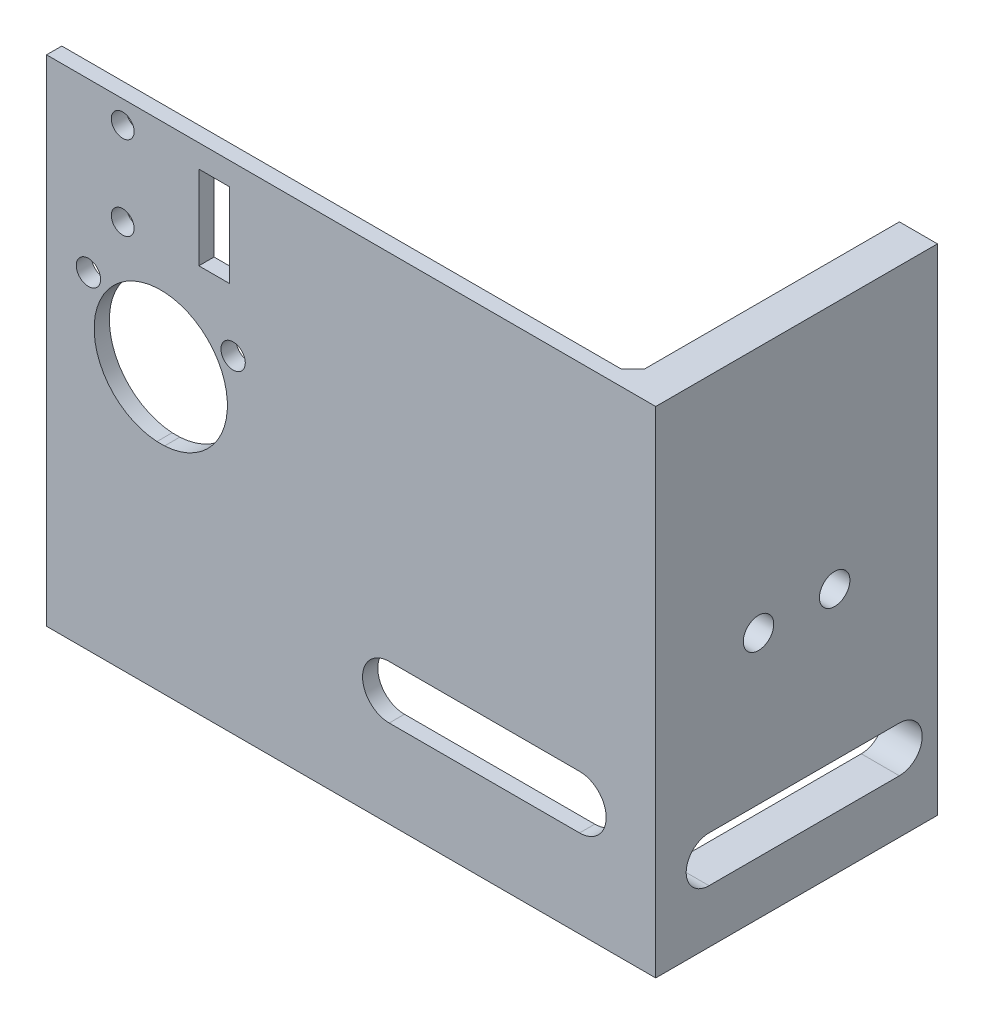
SolidWorks part; units mm, degrees
ref_plane "前视基准面" through (0, 0, 0) normal (0, 0, 1) x (1, 0, 0)
ref_plane "上视基准面" through (0, 0, 0) normal (0, 1, 0) x (1, 0, 0)
ref_plane "右视基准面" through (0, 0, 0) normal (1, 0, 0) x (0, 0, -1)
other "Configuration Table"
sketch "草图1" plane through (0, 0, 0) normal (0, 0, 1) x (1, 0, 0)
  line L1 (-15, 24) -> (15, 24)
  line L2 (-15, 24) -> (-15, -24)
  line L3 (-15, -24) -> (15, -24)
  line L4 (15, 24) -> (15, -24)
  line L5 (-15, 24) -> (15, -24) construction
  line L6 (-15, -24) -> (15, 24) construction
  point P0 (0, 0)
  dimension "D1" = 30
  dimension "D2" = 48
extrude "凸台-拉伸1" add sketch "草图1" against normal blind 2
sketch "草图2" plane through (0, 0, 0) normal (0, 0, 1) x (1, 0, 0)
  line L0 (-9.5, 24) -> (-9.5, -24) construction
  line L1 (15, 24) -> (-15, 24) construction
  line L2 (-15, -24) -> (15, -24) construction
  line L3 (9.5, 24) -> (9.5, -24) construction
  line L4 (15, -24) -> (15, 24) construction
  line L5 (-15, 19) -> (15, 19) construction
  line L6 (-15, 24) -> (-15, -24) construction
  circle A0 centre (-9.5, 19) radius 1.6
  circle A1 centre (9.5, 19) radius 1.6
  point P16 (-9.5, 19)
  point P17 (9.5, 19)
  dimension "D5" = 3.2
  dimension "D1" = 19
  dimension "D2" = 5.5
  dimension "D3" = 5
extrude "切除-拉伸1" cut sketch "草图2" against normal blind 2
sketch "草图3" plane through (0, 0, 0) normal (0, 0, 1) x (1, 0, 0)
  line L0 (-15, 13) -> (15, 13) construction
  line L1 (-15, 24) -> (-15, -24) construction
  line L2 (15, -24) -> (15, 24) construction
  line L4 (-11.1, 19) -> (15, 19) construction
  circle A0 centre (-9.5, 19) radius 1.6 construction
  circle A1 centre (0, 13) radius 8.75
  dimension "D2" = 17.5
  dimension "D1" = 6
extrude "切除-拉伸2" cut sketch "草图3" against normal blind 2
sketch "草图4" plane through (0, 24, 0) normal (0, 1, 0) x (1, 0, 0)
  line L4 (-15, 0) -> (15, 0)
  line L5 (15, 0) -> (15, 2)
  line L6 (15, 2) -> (-15, 2)
  line L7 (-15, 2) -> (-15, 0)
  line L8 (-15, 0) -> (15, 0)
  line L9 (15, 0) -> (15, 2)
  line L10 (15, 2) -> (-15, 2)
  line L11 (-15, 2) -> (-15, 0)
  dimension "D1" = 0
extrude "凸台-拉伸2" add sketch "草图4" along normal blind 17
sketch "草图14" plane through (0, -24, 0) normal (0, -1, 0) x (1, 0, 0)
  line L0 (0, 0) -> (0, -2) construction
  line L1 (-15, 0) -> (15, 0) construction
  line L2 (-15, -2) -> (15, -2) construction
  line L4 (0, 0) -> (-0.5, 0)
  line L5 (0, 0) -> (0, -2)
  line L6 (0, -2) -> (-0.5, -2)
  line L7 (-0.5, 0) -> (-0.5, -2)
  dimension "D1" = 0.5
extrude "切除-拉伸6" cut sketch "草图14" against normal through all
sketch "草图15" plane through (15, 0, 0) normal (1, 0, 0) x (0, 0, -1)
  line L4 (0, 41) -> (0, -24)
  line L5 (0, -24) -> (2, -24)
  line L6 (2, -24) -> (2, 41)
  line L7 (2, 41) -> (0, 41)
  line L8 (0, 41) -> (0, -24)
  line L9 (0, -24) -> (2, -24)
  line L10 (2, -24) -> (2, 41)
  line L11 (2, 41) -> (0, 41)
  dimension "D1" = 0
extrude "凸台-拉伸7" add sketch "草图15" along normal blind 50
sketch "草图16" plane through (0, 0, -2) normal (0, 0, -1) x (-1, 0, 0)
  line L0 (-60, 41) -> (-60, -24) construction
  line L1 (-65, 41) -> (0, 41) construction
  line L2 (0, -24) -> (-65, -24) construction
  line L3 (-65, -24) -> (-65, 41) construction
  line L5 (-65, 41) -> (-60, 41)
  line L6 (-65, 41) -> (-65, -24)
  line L7 (-65, -24) -> (-60, -24)
  line L8 (-60, 41) -> (-60, -24)
  dimension "D1" = 5
extrude "凸台-拉伸8" add sketch "草图16" along normal blind 35
sketch "草图17" plane through (65, 0, 0) normal (1, 0, 0) x (0, 0, -1)
  line L0 (37, 8.5) -> (0, 8.5) construction
  line L1 (37, 41) -> (37, -24) construction
  line L2 (0, 41) -> (0, -24) construction
  line L3 (18.5, 41) -> (18.5, -24) construction
  line L4 (37, 41) -> (0, 41) construction
  line L5 (0, -24) -> (37, -24) construction
  line L6 (13.5, 41) -> (13.5, -24) construction
  line L7 (23.5, 41) -> (23.5, -24) construction
  circle A0 centre (13.5, 8.5) radius 2
  circle A1 centre (23.5, 8.5) radius 2
  point P16 (13.5, 8.5)
  point P17 (23.5, 8.5)
  dimension "D3" = 4
  dimension "D1" = 10
  dimension "D2" = 5
extrude "切除-拉伸7" cut sketch "草图17" against normal blind 35
sketch "草图18" plane through (-0.5, 0, 0) normal (1, 0, 0) x (0, 0, -1)
  line L4 (0, 4.2643) -> (0, -24)
  line L5 (0, -24) -> (2, -24)
  line L6 (2, -24) -> (2, 4.2643)
  line L7 (2, 4.2643) -> (0, 4.2643)
  line L8 (0, 4.2643) -> (0, -24)
  line L9 (0, -24) -> (2, -24)
  line L10 (2, -24) -> (2, 4.2643)
  line L11 (2, 4.2643) -> (0, 4.2643)
  dimension "D1" = 0
extrude "凸台-拉伸9" add sketch "草图18" along normal up to next
sketch "草图19" plane through (-0.5, 0, 0) normal (1, 0, 0) x (0, 0, -1)
  line L4 (2, 21.7357) -> (2, 41)
  line L5 (2, 41) -> (0, 41)
  line L6 (0, 41) -> (0, 21.7357)
  line L7 (0, 21.7357) -> (2, 21.7357)
  line L8 (2, 21.7357) -> (2, 41)
  line L9 (2, 41) -> (0, 41)
  line L10 (0, 41) -> (0, 21.7357)
  line L11 (0, 21.7357) -> (2, 21.7357)
  dimension "D1" = 0
extrude "凸台-拉伸10" add sketch "草图19" along normal up to next
sketch "草图20" plane through (0, 0, 0) normal (0, 0, 1) x (1, 0, 0)
  line L0 (30, 41) -> (30, -24) construction
  line L1 (-15, 41) -> (65, 41) construction
  line L2 (-15, -24) -> (65, -24) construction
  line L3 (-15, -9) -> (65, -9) construction
  line L4 (-15, 41) -> (-15, -24) construction
  line L5 (65, 41) -> (65, -24) construction
  line L6 (55, 41) -> (55, -24) construction
  line L7 (30, -9) -> (55, -9) construction
  line L8 (30, -5.5) -> (55, -5.5)
  line L9 (30, -12.5) -> (55, -12.5)
  arc A0 (30, -5.5) -> (30, -12.5) centre (30, -9) ccw
  arc A1 (55, -12.5) -> (55, -5.5) centre (55, -9) ccw
  point P14 (30, -9)
  point P15 (55, -9)
  point P18 (42.5, -9)
  dimension "D4" = 3.5
  dimension "D1" = 25
  dimension "D2" = 10
  dimension "D3" = 15
extrude "切除-拉伸8" cut sketch "草图20" against normal blind 6
sketch "草图21" plane through (65, 0, 0) normal (1, 0, 0) x (0, 0, -1)
  line L0 (0, -14) -> (37, -14) construction
  line L1 (0, 41) -> (0, -24) construction
  line L2 (37, 41) -> (37, -24) construction
  line L3 (7, 40.7245) -> (7, -24) construction
  line L4 (0, -24) -> (37, -24) construction
  line L5 (32, 41) -> (32, -24) construction
  line L6 (37, 41) -> (0, 41) construction
  line L7 (7, -14) -> (32, -14) construction
  line L8 (7, -11) -> (32, -11)
  line L9 (7, -17) -> (32, -17)
  arc A0 (7, -11) -> (7, -17) centre (7, -14) ccw
  arc A1 (32, -17) -> (32, -11) centre (32, -14) ccw
  point P14 (7, -14)
  point P15 (32, -14)
  point P18 (19.5, -14)
  dimension "D4" = 3
  dimension "D1" = 25
  dimension "D2" = 5
  dimension "D3" = 10
extrude "切除-拉伸9" cut sketch "草图21" against normal blind 6
chamfer "倒角1" distance 1.5 angle 45 1 edges at (60, 8.5, -2)
sketch "草图22" plane through (0, 0, 0) normal (0, 0, 1) x (1, 0, 0)
  line L0 (-15, 38) -> (65, 38) construction
  line L1 (-15, 41) -> (-15, -24) construction
  line L2 (65, 41) -> (65, -24) construction
  line L3 (-5, 41) -> (-5, -24) construction
  line L4 (-15, 41) -> (65, 41) construction
  line L5 (-15, -24) -> (65, -24) construction
  line L6 (5, 41) -> (5, -24) construction
  line L7 (-15, 27) -> (65, 27) construction
  line L8 (9, 41) -> (9, -24) construction
  line L14 (5, 38) -> (9, 38)
  line L15 (5, 38) -> (5, 27)
  line L16 (5, 27) -> (9, 27)
  line L17 (9, 38) -> (9, 27)
  circle A0 centre (-5, 38) radius 1.5
  circle A1 centre (-5, 27) radius 1.5
  point P16 (-5, 38)
  point P17 (-5, 27)
  point P24 (5, 38)
  point P25 (9, 27)
  dimension "D5" = 3
  dimension "D1" = 10
  dimension "D2" = 11
  dimension "D3" = 3
  dimension "D4" = 10
  dimension "D6" = 4
extrude "切除-拉伸10" cut sketch "草图22" against normal through all
